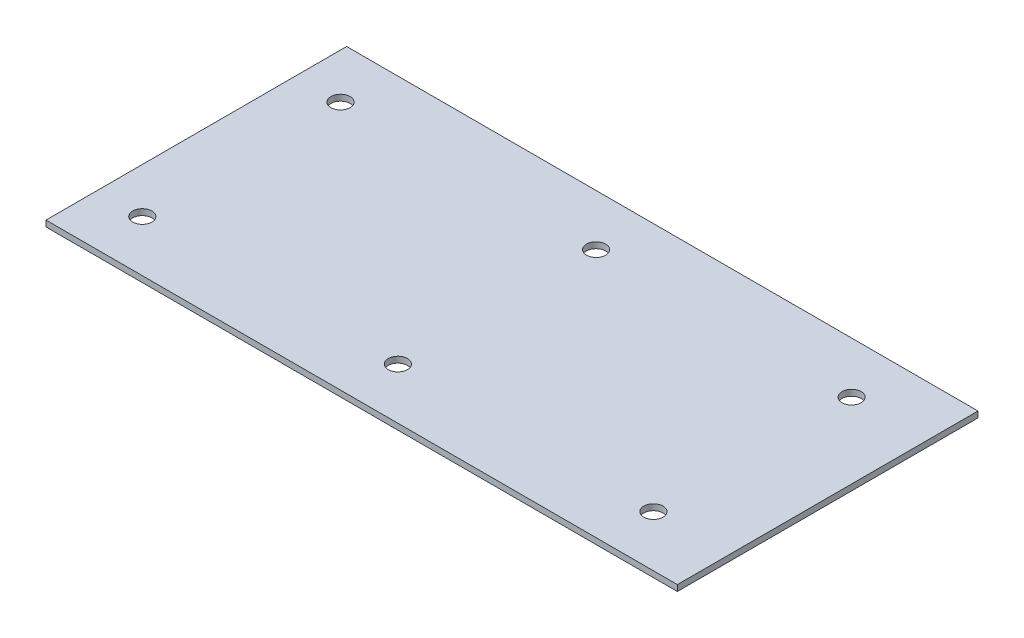
SolidWorks part; units mm, degrees
ref_plane "Спереди" through (0, 0, 0) normal (0, 0, 1) x (1, 0, 0)
ref_plane "Сверху" through (0, 0, 0) normal (0, 1, 0) x (1, 0, 0)
ref_plane "Справа" through (0, 0, 0) normal (1, 0, 0) x (0, 0, -1)
sketch "Эскиз1" plane through (0, 0, 0) normal (0, 1, 0) x (1, 0, 0)
  line L0 (15, 17.0342) -> (185, 17.0342) construction
  line L5 (0, 0) -> (210, 0)
  line L6 (0, 0) -> (0, 100)
  line L7 (0, 100) -> (210, 100)
  line L8 (210, 0) -> (210, 100)
  line L9 (0, 50) -> (210, 50) construction
  circle A0 centre (185, 17.0342) radius 3.2
  circle A1 centre (100, 17.0342) radius 3.2
  circle A2 centre (15, 17.0342) radius 3.2
  circle A3 centre (185, 82.9658) radius 3.2
  circle A4 centre (100, 82.9658) radius 3.2
  circle A5 centre (15, 82.9658) radius 3.2
  dimension "D1" = 210
  dimension "D2" = 100
extrude "Бобышка-Вытянуть1" add sketch "Эскиз1" along normal blind 2
